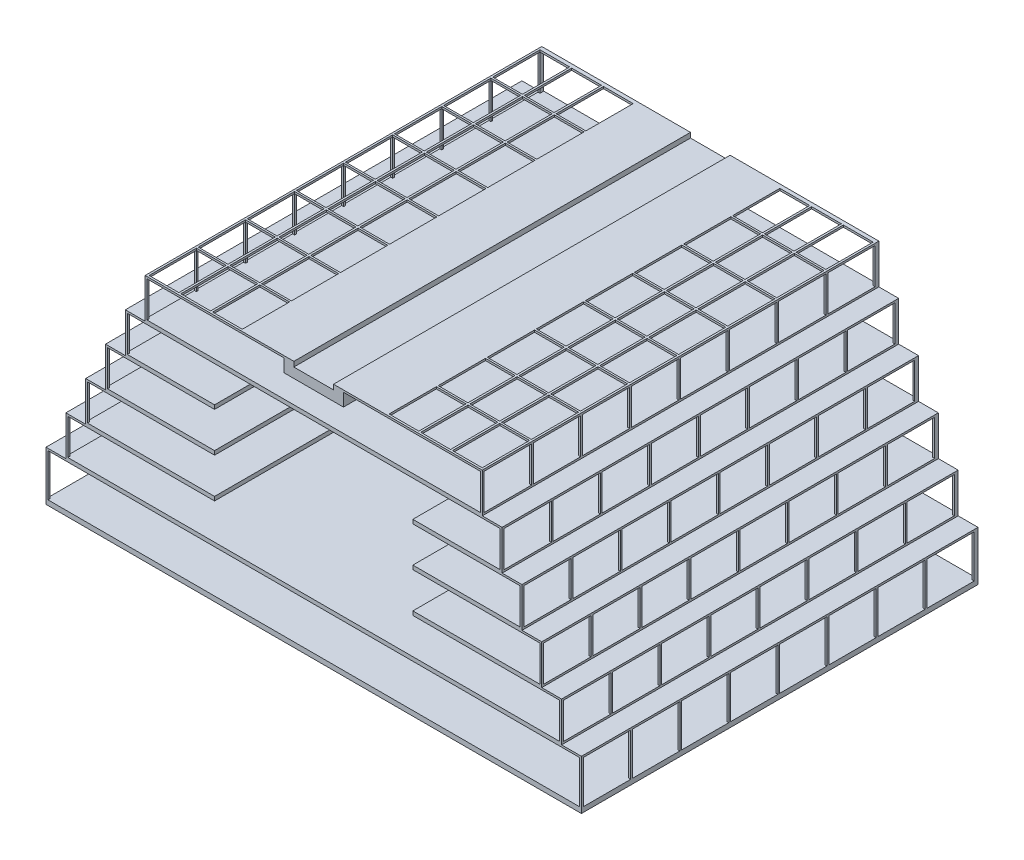
SolidWorks part; units mm, degrees
ref_plane "前视基准面" through (0, 0, 0) normal (0, 0, 1) x (1, 0, 0)
ref_plane "上视基准面" through (0, 0, 0) normal (0, 1, 0) x (1, 0, 0)
ref_plane "右视基准面" through (0, 0, 0) normal (1, 0, 0) x (0, 0, -1)
sketch "草图1" plane through (0, 0, 0) normal (0, 0, 1) x (1, 0, 0)
  line L0 (0, 14.7003) -> (0, 72.5993) construction
  line L1 (0, 24.5) -> (2, 24.5)
  line L2 (2, 24.5) -> (2, 25)
  line L3 (2, 25) -> (17, 25)
  line L4 (17, 25) -> (17, 21)
  line L5 (17, 21) -> (19, 21)
  line L6 (19, 21) -> (19, 17)
  line L7 (19, 17) -> (21, 17)
  line L8 (21, 17) -> (21, 13)
  line L9 (21, 13) -> (23, 13)
  line L10 (23, 13) -> (23, 9)
  line L11 (23, 9) -> (25, 9)
  line L12 (25, 9) -> (25, 5)
  line L13 (25, 5) -> (27, 5)
  line L14 (27, 5) -> (27, 0)
  line L15 (0, 0) -> (27, 0)
  line L16 (-18.299, 40) -> (31.6769, 40) construction
  line L17 (0, 24.5) -> (0, 0)
  dimension "D1" = 40
  dimension "D2" = 25
  dimension "D3" = 2
  dimension "D4" = 0.5
  dimension "D5" = 27
  dimension "D6" = 4
  dimension "D7" = 4
  dimension "D8" = 4
  dimension "D9" = 4
  dimension "D10" = 4
  dimension "D11" = 2
  dimension "D12" = 2
  dimension "D13" = 2
  dimension "D14" = 2
  dimension "D15" = 2
extrude "凸台-拉伸1" add sketch "草图1" against normal blind 40
sketch "草图2" plane through (17, 0, 0) normal (1, 0, 0) x (0, 0, -1)
  line L0 (40, 25) -> (0, 25) construction
  line L1 (0.2, 24.8) -> (4.97, 24.8)
  line L2 (0.2, 24.8) -> (0.2, 21.2)
  line L3 (0.2, 21.2) -> (4.97, 21.2)
  line L4 (4.97, 24.8) -> (4.97, 21.2)
  line L5 (0, 21) -> (0, 25) construction
  line L6 (5.15, 24.8) -> (5.15, 21.2)
  line L7 (5.15, 24.8) -> (9.92, 24.8)
  line L8 (9.92, 24.8) -> (9.92, 21.2)
  line L9 (5.15, 21.2) -> (9.92, 21.2)
  line L10 (10.1, 24.8) -> (10.1, 21.2)
  line L11 (10.1, 24.8) -> (14.87, 24.8)
  line L12 (14.87, 24.8) -> (14.87, 21.2)
  line L13 (10.1, 21.2) -> (14.87, 21.2)
  line L14 (15.05, 24.8) -> (15.05, 21.2)
  line L15 (15.05, 24.8) -> (19.82, 24.8)
  line L16 (19.82, 24.8) -> (19.82, 21.2)
  line L17 (15.05, 21.2) -> (19.82, 21.2)
  line L18 (20, 24.8) -> (20, 21.2)
  line L19 (20, 24.8) -> (24.77, 24.8)
  line L20 (24.77, 24.8) -> (24.77, 21.2)
  line L21 (20, 21.2) -> (24.77, 21.2)
  line L22 (24.95, 24.8) -> (24.95, 21.2)
  line L23 (24.95, 24.8) -> (29.72, 24.8)
  line L24 (29.72, 24.8) -> (29.72, 21.2)
  line L25 (24.95, 21.2) -> (29.72, 21.2)
  line L26 (29.9, 24.8) -> (29.9, 21.2)
  line L27 (29.9, 24.8) -> (34.67, 24.8)
  line L28 (34.67, 24.8) -> (34.67, 21.2)
  line L29 (29.9, 21.2) -> (34.67, 21.2)
  line L30 (34.85, 24.8) -> (34.85, 21.2)
  line L31 (34.85, 24.8) -> (39.62, 24.8)
  line L32 (39.62, 24.8) -> (39.62, 21.2)
  line L33 (34.85, 21.2) -> (39.62, 21.2)
  dimension "D1" = 4.77
  dimension "D2" = 3.6
  dimension "D3" = 0.2
  dimension "D4" = 0.2
  dimension "D5" = 8
extrude "切除-拉伸1" cut sketch "草图2" against normal blind 11
sketch "草图3" plane through (0, 25, 0) normal (0, 1, 0) x (1, 0, 0)
  line L0 (17, 0) -> (2, 0) construction
  line L1 (13.8, 4.97) -> (16.8, 4.97)
  line L2 (13.8, 4.97) -> (13.8, 0.2)
  line L3 (13.8, 0.2) -> (16.8, 0.2)
  line L4 (16.8, 4.97) -> (16.8, 0.2)
  line L5 (17, 40) -> (17, 0) construction
  line L6 (6, 4.97) -> (17, 4.97) construction
  line L7 (13.8, 9.92) -> (13.8, 5.15)
  line L8 (13.8, 9.92) -> (16.8, 9.92)
  line L9 (16.8, 9.92) -> (16.8, 5.15)
  line L10 (13.8, 5.15) -> (16.8, 5.15)
  line L11 (13.8, 14.87) -> (13.8, 10.1)
  line L12 (13.8, 14.87) -> (16.8, 14.87)
  line L13 (16.8, 14.87) -> (16.8, 10.1)
  line L14 (13.8, 10.1) -> (16.8, 10.1)
  line L15 (13.8, 19.82) -> (13.8, 15.05)
  line L16 (13.8, 19.82) -> (16.8, 19.82)
  line L17 (16.8, 19.82) -> (16.8, 15.05)
  line L18 (13.8, 15.05) -> (16.8, 15.05)
  line L19 (13.8, 24.77) -> (13.8, 20)
  line L20 (13.8, 24.77) -> (16.8, 24.77)
  line L21 (16.8, 24.77) -> (16.8, 20)
  line L22 (13.8, 20) -> (16.8, 20)
  line L23 (13.8, 29.72) -> (13.8, 24.95)
  line L24 (13.8, 29.72) -> (16.8, 29.72)
  line L25 (16.8, 29.72) -> (16.8, 24.95)
  line L26 (13.8, 24.95) -> (16.8, 24.95)
  line L27 (13.8, 34.67) -> (13.8, 29.9)
  line L28 (13.8, 34.67) -> (16.8, 34.67)
  line L29 (16.8, 34.67) -> (16.8, 29.9)
  line L30 (13.8, 29.9) -> (16.8, 29.9)
  line L31 (13.8, 39.62) -> (13.8, 34.85)
  line L32 (13.8, 39.62) -> (16.8, 39.62)
  line L33 (16.8, 39.62) -> (16.8, 34.85)
  line L34 (13.8, 34.85) -> (16.8, 34.85)
  line L35 (10.6, 4.97) -> (10.6, 0.2)
  line L36 (10.6, 4.97) -> (13.6, 4.97)
  line L37 (13.6, 4.97) -> (13.6, 0.2)
  line L38 (10.6, 0.2) -> (13.6, 0.2)
  line L39 (10.6, 9.92) -> (10.6, 5.15)
  line L40 (10.6, 5.15) -> (13.6, 5.15)
  line L41 (13.6, 9.92) -> (13.6, 5.15)
  line L42 (10.6, 9.92) -> (13.6, 9.92)
  line L43 (10.6, 14.87) -> (10.6, 10.1)
  line L44 (10.6, 10.1) -> (13.6, 10.1)
  line L45 (13.6, 14.87) -> (13.6, 10.1)
  line L46 (10.6, 14.87) -> (13.6, 14.87)
  line L47 (10.6, 19.82) -> (10.6, 15.05)
  line L48 (10.6, 15.05) -> (13.6, 15.05)
  line L49 (13.6, 19.82) -> (13.6, 15.05)
  line L50 (10.6, 19.82) -> (13.6, 19.82)
  line L51 (10.6, 24.77) -> (10.6, 20)
  line L52 (10.6, 20) -> (13.6, 20)
  line L53 (13.6, 24.77) -> (13.6, 20)
  line L54 (10.6, 24.77) -> (13.6, 24.77)
  line L55 (10.6, 29.72) -> (10.6, 24.95)
  line L56 (10.6, 24.95) -> (13.6, 24.95)
  line L57 (13.6, 29.72) -> (13.6, 24.95)
  line L58 (10.6, 29.72) -> (13.6, 29.72)
  line L59 (10.6, 34.67) -> (10.6, 29.9)
  line L60 (10.6, 29.9) -> (13.6, 29.9)
  line L61 (13.6, 34.67) -> (13.6, 29.9)
  line L62 (10.6, 34.67) -> (13.6, 34.67)
  line L63 (10.6, 39.62) -> (10.6, 34.85)
  line L64 (10.6, 34.85) -> (13.6, 34.85)
  line L65 (13.6, 39.62) -> (13.6, 34.85)
  line L66 (10.6, 39.62) -> (13.6, 39.62)
  line L67 (7.4, 4.97) -> (7.4, 0.2)
  line L68 (7.4, 4.97) -> (10.4, 4.97)
  line L69 (10.4, 4.97) -> (10.4, 0.2)
  line L70 (7.4, 0.2) -> (10.4, 0.2)
  line L71 (7.4, 9.92) -> (7.4, 5.15)
  line L72 (7.4, 5.15) -> (10.4, 5.15)
  line L73 (10.4, 9.92) -> (10.4, 5.15)
  line L74 (7.4, 9.92) -> (10.4, 9.92)
  line L75 (7.4, 14.87) -> (7.4, 10.1)
  line L76 (7.4, 10.1) -> (10.4, 10.1)
  line L77 (10.4, 14.87) -> (10.4, 10.1)
  line L78 (7.4, 14.87) -> (10.4, 14.87)
  line L79 (7.4, 19.82) -> (7.4, 15.05)
  line L80 (7.4, 15.05) -> (10.4, 15.05)
  line L81 (10.4, 19.82) -> (10.4, 15.05)
  line L82 (7.4, 19.82) -> (10.4, 19.82)
  line L83 (7.4, 24.77) -> (7.4, 20)
  line L84 (7.4, 20) -> (10.4, 20)
  line L85 (10.4, 24.77) -> (10.4, 20)
  line L86 (7.4, 24.77) -> (10.4, 24.77)
  line L87 (7.4, 29.72) -> (7.4, 24.95)
  line L88 (7.4, 24.95) -> (10.4, 24.95)
  line L89 (10.4, 29.72) -> (10.4, 24.95)
  line L90 (7.4, 29.72) -> (10.4, 29.72)
  line L91 (7.4, 34.67) -> (7.4, 29.9)
  line L92 (7.4, 29.9) -> (10.4, 29.9)
  line L93 (10.4, 34.67) -> (10.4, 29.9)
  line L94 (7.4, 34.67) -> (10.4, 34.67)
  line L95 (7.4, 39.62) -> (7.4, 34.85)
  line L96 (7.4, 34.85) -> (10.4, 34.85)
  line L97 (10.4, 39.62) -> (10.4, 34.85)
  line L98 (7.4, 39.62) -> (10.4, 39.62)
  dimension "D1" = 0.2
  dimension "D2" = 0.2
  dimension "D3" = 3
  dimension "D4" = 8
  dimension "D5" = 3
extrude "切除-拉伸2" cut sketch "草图3" against normal up to next
sketch "草图4" plane through (19, 0, 0) normal (1, 0, 0) x (0, 0, -1)
  line L0 (0.2, 24.8) -> (0.2, 21.2) construction
  line L1 (0.2, 20.8) -> (4.97, 20.8)
  line L2 (0.2, 20.8) -> (0.2, 17.2)
  line L3 (0.2, 17.2) -> (4.97, 17.2)
  line L4 (4.97, 20.8) -> (4.97, 17.2)
  line L5 (4.97, 21.2) -> (4.97, 24.8) construction
  line L6 (40, 21) -> (0, 21) construction
  line L7 (40, 17) -> (0, 17) construction
  line L8 (5.15, 20.8) -> (5.15, 17.2)
  line L9 (5.15, 20.8) -> (9.92, 20.8)
  line L10 (9.92, 20.8) -> (9.92, 17.2)
  line L11 (5.15, 17.2) -> (9.92, 17.2)
  line L12 (10.1, 20.8) -> (10.1, 17.2)
  line L13 (10.1, 20.8) -> (14.87, 20.8)
  line L14 (14.87, 20.8) -> (14.87, 17.2)
  line L15 (10.1, 17.2) -> (14.87, 17.2)
  line L16 (15.05, 20.8) -> (15.05, 17.2)
  line L17 (15.05, 20.8) -> (19.82, 20.8)
  line L18 (19.82, 20.8) -> (19.82, 17.2)
  line L19 (15.05, 17.2) -> (19.82, 17.2)
  line L20 (20, 20.8) -> (20, 17.2)
  line L21 (20, 20.8) -> (24.77, 20.8)
  line L22 (24.77, 20.8) -> (24.77, 17.2)
  line L23 (20, 17.2) -> (24.77, 17.2)
  line L24 (24.95, 20.8) -> (24.95, 17.2)
  line L25 (24.95, 20.8) -> (29.72, 20.8)
  line L26 (29.72, 20.8) -> (29.72, 17.2)
  line L27 (24.95, 17.2) -> (29.72, 17.2)
  line L28 (29.9, 20.8) -> (29.9, 17.2)
  line L29 (29.9, 20.8) -> (34.67, 20.8)
  line L30 (34.67, 20.8) -> (34.67, 17.2)
  line L31 (29.9, 17.2) -> (34.67, 17.2)
  line L32 (34.85, 20.8) -> (34.85, 17.2)
  line L33 (34.85, 20.8) -> (39.62, 20.8)
  line L34 (39.62, 20.8) -> (39.62, 17.2)
  line L35 (34.85, 17.2) -> (39.62, 17.2)
  dimension "D1" = 0.2
  dimension "D2" = 0.2
  dimension "D3" = 8
extrude "切除-拉伸3" cut sketch "草图4" against normal blind 11
sketch "草图5" plane through (21, 0, 0) normal (1, 0, 0) x (0, 0, -1)
  line L0 (40, 17) -> (0, 17) construction
  line L1 (0.2, 16.8) -> (4.97, 16.8)
  line L2 (0.2, 16.8) -> (0.2, 13.2)
  line L3 (0.2, 13.2) -> (4.97, 13.2)
  line L4 (4.97, 16.8) -> (4.97, 13.2)
  line L5 (40, 13) -> (0, 13) construction
  line L6 (0.2, 20.8) -> (0.2, 17.2) construction
  line L7 (4.97, 17.2) -> (4.97, 20.8) construction
  line L8 (5.15, 16.8) -> (5.15, 13.2)
  line L9 (5.15, 16.8) -> (9.92, 16.8)
  line L10 (9.92, 16.8) -> (9.92, 13.2)
  line L11 (5.15, 13.2) -> (9.92, 13.2)
  line L12 (10.1, 16.8) -> (10.1, 13.2)
  line L13 (10.1, 16.8) -> (14.87, 16.8)
  line L14 (14.87, 16.8) -> (14.87, 13.2)
  line L15 (10.1, 13.2) -> (14.87, 13.2)
  line L16 (15.05, 16.8) -> (15.05, 13.2)
  line L17 (15.05, 16.8) -> (19.82, 16.8)
  line L18 (19.82, 16.8) -> (19.82, 13.2)
  line L19 (15.05, 13.2) -> (19.82, 13.2)
  line L20 (20, 16.8) -> (20, 13.2)
  line L21 (20, 16.8) -> (24.77, 16.8)
  line L22 (24.77, 16.8) -> (24.77, 13.2)
  line L23 (20, 13.2) -> (24.77, 13.2)
  line L24 (24.95, 16.8) -> (24.95, 13.2)
  line L25 (24.95, 16.8) -> (29.72, 16.8)
  line L26 (29.72, 16.8) -> (29.72, 13.2)
  line L27 (24.95, 13.2) -> (29.72, 13.2)
  line L28 (29.9, 16.8) -> (29.9, 13.2)
  line L29 (29.9, 16.8) -> (34.67, 16.8)
  line L30 (34.67, 16.8) -> (34.67, 13.2)
  line L31 (29.9, 13.2) -> (34.67, 13.2)
  line L32 (34.85, 16.8) -> (34.85, 13.2)
  line L33 (34.85, 16.8) -> (39.62, 16.8)
  line L34 (39.62, 16.8) -> (39.62, 13.2)
  line L35 (34.85, 13.2) -> (39.62, 13.2)
  dimension "D1" = 0.2
  dimension "D2" = 0.2
  dimension "D3" = 8
extrude "切除-拉伸4" cut sketch "草图5" against normal blind 11
sketch "草图6" plane through (23, 0, 0) normal (1, 0, 0) x (0, 0, -1)
  line L0 (40, 13) -> (0, 13) construction
  line L1 (0.2, 12.8) -> (4.97, 12.8)
  line L2 (0.2, 12.8) -> (0.2, 9.2)
  line L3 (0.2, 9.2) -> (4.97, 9.2)
  line L4 (4.97, 12.8) -> (4.97, 9.2)
  line L5 (40, 9) -> (0, 9) construction
  line L6 (0.2, 16.8) -> (0.2, 13.2) construction
  line L7 (4.97, 13.2) -> (4.97, 16.8) construction
  line L8 (5.15, 12.8) -> (5.15, 9.2)
  line L9 (5.15, 12.8) -> (9.92, 12.8)
  line L10 (9.92, 12.8) -> (9.92, 9.2)
  line L11 (5.15, 9.2) -> (9.92, 9.2)
  line L12 (10.1, 12.8) -> (10.1, 9.2)
  line L13 (10.1, 12.8) -> (14.87, 12.8)
  line L14 (14.87, 12.8) -> (14.87, 9.2)
  line L15 (10.1, 9.2) -> (14.87, 9.2)
  line L16 (15.05, 12.8) -> (15.05, 9.2)
  line L17 (15.05, 12.8) -> (19.82, 12.8)
  line L18 (19.82, 12.8) -> (19.82, 9.2)
  line L19 (15.05, 9.2) -> (19.82, 9.2)
  line L20 (20, 12.8) -> (20, 9.2)
  line L21 (20, 12.8) -> (24.77, 12.8)
  line L22 (24.77, 12.8) -> (24.77, 9.2)
  line L23 (20, 9.2) -> (24.77, 9.2)
  line L24 (24.95, 12.8) -> (24.95, 9.2)
  line L25 (24.95, 12.8) -> (29.72, 12.8)
  line L26 (29.72, 12.8) -> (29.72, 9.2)
  line L27 (24.95, 9.2) -> (29.72, 9.2)
  line L28 (29.9, 12.8) -> (29.9, 9.2)
  line L29 (29.9, 12.8) -> (34.67, 12.8)
  line L30 (34.67, 12.8) -> (34.67, 9.2)
  line L31 (29.9, 9.2) -> (34.67, 9.2)
  line L32 (34.85, 12.8) -> (34.85, 9.2)
  line L33 (34.85, 12.8) -> (39.62, 12.8)
  line L34 (39.62, 12.8) -> (39.62, 9.2)
  line L35 (34.85, 9.2) -> (39.62, 9.2)
  dimension "D1" = 0.2
  dimension "D2" = 0.2
  dimension "D3" = 8
extrude "切除-拉伸5" cut sketch "草图6" against normal blind 11
sketch "草图7" plane through (25, 0, 0) normal (1, 0, 0) x (0, 0, -1)
  line L0 (40, 9) -> (0, 9) construction
  line L1 (0.2, 8.8) -> (4.97, 8.8)
  line L2 (0.2, 8.8) -> (0.2, 5.2)
  line L3 (0.2, 5.2) -> (4.97, 5.2)
  line L4 (4.97, 8.8) -> (4.97, 5.2)
  line L5 (40, 5) -> (0, 5) construction
  line L8 (0.2, 12.8) -> (0.2, 9.2) construction
  line L9 (4.97, 9.2) -> (4.97, 12.8) construction
  line L10 (5.15, 8.8) -> (5.15, 5.2)
  line L11 (5.15, 8.8) -> (9.92, 8.8)
  line L12 (9.92, 8.8) -> (9.92, 5.2)
  line L13 (5.15, 5.2) -> (9.92, 5.2)
  line L14 (10.1, 8.8) -> (10.1, 5.2)
  line L15 (10.1, 8.8) -> (14.87, 8.8)
  line L16 (14.87, 8.8) -> (14.87, 5.2)
  line L17 (10.1, 5.2) -> (14.87, 5.2)
  line L18 (15.05, 8.8) -> (15.05, 5.2)
  line L19 (15.05, 8.8) -> (19.82, 8.8)
  line L20 (19.82, 8.8) -> (19.82, 5.2)
  line L21 (15.05, 5.2) -> (19.82, 5.2)
  line L22 (20, 8.8) -> (20, 5.2)
  line L23 (20, 8.8) -> (24.77, 8.8)
  line L24 (24.77, 8.8) -> (24.77, 5.2)
  line L25 (20, 5.2) -> (24.77, 5.2)
  line L26 (24.95, 8.8) -> (24.95, 5.2)
  line L27 (24.95, 8.8) -> (29.72, 8.8)
  line L28 (29.72, 8.8) -> (29.72, 5.2)
  line L29 (24.95, 5.2) -> (29.72, 5.2)
  line L30 (29.9, 8.8) -> (29.9, 5.2)
  line L31 (29.9, 8.8) -> (34.67, 8.8)
  line L32 (34.67, 8.8) -> (34.67, 5.2)
  line L33 (29.9, 5.2) -> (34.67, 5.2)
  line L34 (34.85, 8.8) -> (34.85, 5.2)
  line L35 (34.85, 8.8) -> (39.62, 8.8)
  line L36 (39.62, 8.8) -> (39.62, 5.2)
  line L37 (34.85, 5.2) -> (39.62, 5.2)
  line L38 (0.2, 8.8) -> (5.15, 8.8) construction
  dimension "D1" = 0.2
  dimension "D2" = 0.2
  dimension "D4" = 4.95
  dimension "D3" = 8
extrude "切除-拉伸6" cut sketch "草图7" against normal blind 11
sketch "草图8" plane through (27, 0, 0) normal (1, 0, 0) x (0, 0, -1)
  line L0 (0.2, 8.8) -> (0.2, 5.2) construction
  line L1 (0.2, 4.8) -> (4.97, 4.8)
  line L2 (0.2, 4.8) -> (0.2, 0.5)
  line L3 (0.2, 0.5) -> (4.97, 0.5)
  line L4 (4.97, 4.8) -> (4.97, 0.5)
  line L5 (4.97, 5.2) -> (4.97, 8.8) construction
  line L6 (40, 5) -> (0, 5) construction
  line L7 (40, 0) -> (0, 0) construction
  line L8 (5.15, 4.8) -> (5.15, 0.5)
  line L9 (5.15, 4.8) -> (9.92, 4.8)
  line L10 (9.92, 4.8) -> (9.92, 0.5)
  line L11 (5.15, 0.5) -> (9.92, 0.5)
  line L12 (10.1, 4.8) -> (10.1, 0.5)
  line L13 (10.1, 4.8) -> (14.87, 4.8)
  line L14 (14.87, 4.8) -> (14.87, 0.5)
  line L15 (10.1, 0.5) -> (14.87, 0.5)
  line L16 (15.05, 4.8) -> (15.05, 0.5)
  line L17 (15.05, 4.8) -> (19.82, 4.8)
  line L18 (19.82, 4.8) -> (19.82, 0.5)
  line L19 (15.05, 0.5) -> (19.82, 0.5)
  line L20 (20, 4.8) -> (20, 0.5)
  line L21 (20, 4.8) -> (24.77, 4.8)
  line L22 (24.77, 4.8) -> (24.77, 0.5)
  line L23 (20, 0.5) -> (24.77, 0.5)
  line L24 (24.95, 4.8) -> (24.95, 0.5)
  line L25 (24.95, 4.8) -> (29.72, 4.8)
  line L26 (29.72, 4.8) -> (29.72, 0.5)
  line L27 (24.95, 0.5) -> (29.72, 0.5)
  line L28 (29.9, 4.8) -> (29.9, 0.5)
  line L29 (29.9, 4.8) -> (34.67, 4.8)
  line L30 (34.67, 4.8) -> (34.67, 0.5)
  line L31 (29.9, 0.5) -> (34.67, 0.5)
  line L32 (34.85, 4.8) -> (34.85, 0.5)
  line L33 (34.85, 4.8) -> (39.62, 4.8)
  line L34 (39.62, 4.8) -> (39.62, 0.5)
  line L35 (34.85, 0.5) -> (39.62, 0.5)
  line L36 (0.2, 4.8) -> (5.15, 4.8) construction
  dimension "D1" = 0.2
  dimension "D2" = 0.5
  dimension "D4" = 4.95
  dimension "D3" = 8
extrude "切除-拉伸7" cut sketch "草图8" against normal blind 11
mirror "镜向1" about plane through (0, 0, 0) normal (1, 0, 0) of "切除-拉伸7", "凸台-拉伸1", "切除-拉伸4", "切除-拉伸1", "切除-拉伸2", "切除-拉伸3", "切除-拉伸5", "切除-拉伸6"
sketch "草图9" plane through (0, 0, 0) normal (0, 0, 1) x (1, 0, 0)
  line L0 (17, 21) -> (17, 25) construction
  line L1 (3, 24.8) -> (16.8, 24.8)
  line L4 (16.8, 24.8) -> (16.8, 21.2)
  line L5 (17, 25) -> (2, 25) construction
  line L6 (21, 13) -> (21, 17) construction
  line L7 (16.8, 21.2) -> (-16.8, 21.2)
  line L8 (16, 0.5) -> (27, 0.5) construction
  line L9 (-18.8, 20.8) -> (18.8, 20.8)
  line L10 (18.8, 20.8) -> (18.8, 17.2)
  line L11 (-20.8, 16.8) -> (20.8, 16.8)
  line L12 (20.8, 16.8) -> (20.8, 13.2)
  line L13 (-22.8, 12.8) -> (22.8, 12.8)
  line L14 (22.8, 12.8) -> (22.8, 9.2)
  line L15 (-24.8, 8.8) -> (24.8, 8.8)
  line L16 (24.8, 8.8) -> (24.8, 5.2)
  line L17 (-26.8, 4.8) -> (26.8, 4.8)
  line L18 (26.8, 4.8) -> (26.8, 0.5)
  line L19 (26.8, 0.5) -> (-26.8, 0.5)
  line L20 (19, 21) -> (17, 21) construction
  line L21 (19, 17) -> (19, 21) construction
  line L22 (21, 17) -> (19, 17) construction
  line L23 (23, 13) -> (21, 13) construction
  line L24 (23, 9) -> (23, 13) construction
  line L25 (25, 9) -> (23, 9) construction
  line L26 (25, 5) -> (25, 9) construction
  line L27 (27, 0) -> (27, 5) construction
  line L28 (27, 5) -> (25, 5) construction
  line L29 (3, 24.8) -> (3, 23.5)
  line L30 (3, 23.5) -> (-3, 23.5)
  line L31 (2, 24.5) -> (-2, 24.5) construction
  line L32 (2, 25) -> (2, 24.5) construction
  line L33 (18.8, 17.2) -> (-18.8, 17.2)
  line L34 (20.8, 13.2) -> (-20.8, 13.2)
  line L35 (22.8, 9.2) -> (-22.8, 9.2)
  line L36 (24.8, 5.2) -> (-24.8, 5.2)
  line L37 (6, 21.2) -> (17, 21.2) construction
  line L38 (0, -13.75) -> (0, 13.75) construction
  line L39 (10, 13.2) -> (21, 13.2) construction
  line L40 (12, 9.2) -> (23, 9.2) construction
  line L41 (14, 5.2) -> (25, 5.2) construction
  line L42 (8, 17.2) -> (19, 17.2) construction
  line L43 (-3, 24.8) -> (-3, 23.5)
  line L44 (-26.8, 4.8) -> (-26.8, 0.5)
  line L45 (-24.8, 8.8) -> (-24.8, 5.2)
  line L46 (-22.8, 12.8) -> (-22.8, 9.2)
  line L47 (-20.8, 16.8) -> (-20.8, 13.2)
  line L48 (-18.8, 20.8) -> (-18.8, 17.2)
  line L49 (-16.8, 24.8) -> (-16.8, 21.2)
  line L50 (-3, 24.8) -> (-16.8, 24.8)
  point P65 (0, 0)
  point P68 (0, 0)
  point P69 (0, 0)
  point P73 (0, 5.2)
  point P74 (0, 9.2)
  point P75 (0, 13.2)
  point P76 (0, 17.2)
  point P77 (0, 23.5)
  point P79 (0, 0.5)
  point P80 (0, 4.8)
  point P81 (0, 8.8)
  point P82 (0, 12.8)
  point P83 (0, 16.8)
  point P84 (0, 20.8)
  point P86 (0, 21.2)
  dimension "D1" = 0.2
  dimension "D2" = 0.2
  dimension "D3" = 0.2
  dimension "D4" = 0.2
  dimension "D5" = 0.2
  dimension "D6" = 0.2
  dimension "D7" = 0.2
  dimension "D8" = 0.2
  dimension "D9" = 0.2
  dimension "D10" = 0.2
  dimension "D11" = 0.2
  dimension "D12" = 0.2
  dimension "D13" = 1
  dimension "D14" = 1
extrude "切除-拉伸9" cut sketch "草图9" against normal through all
sketch "草图10" plane through (0, 0, -40) normal (0, 0, -1) x (-1, 0, 0)
  line L0 (-10, 5.2) -> (-10, 17.2)
  line L1 (24.8, 5.2) -> (-24.8, 5.2) construction
  line L2 (-10, 17.2) -> (10, 17.2)
  line L3 (10, 17.2) -> (10, 5.2)
  line L5 (18.8, 17.2) -> (-18.8, 17.2) construction
  line L9 (-10, 5.2) -> (10, 5.2)
  dimension "D1" = 10
  dimension "D2" = 20
extrude "切除-拉伸10" cut sketch "草图10" against normal blind 49
